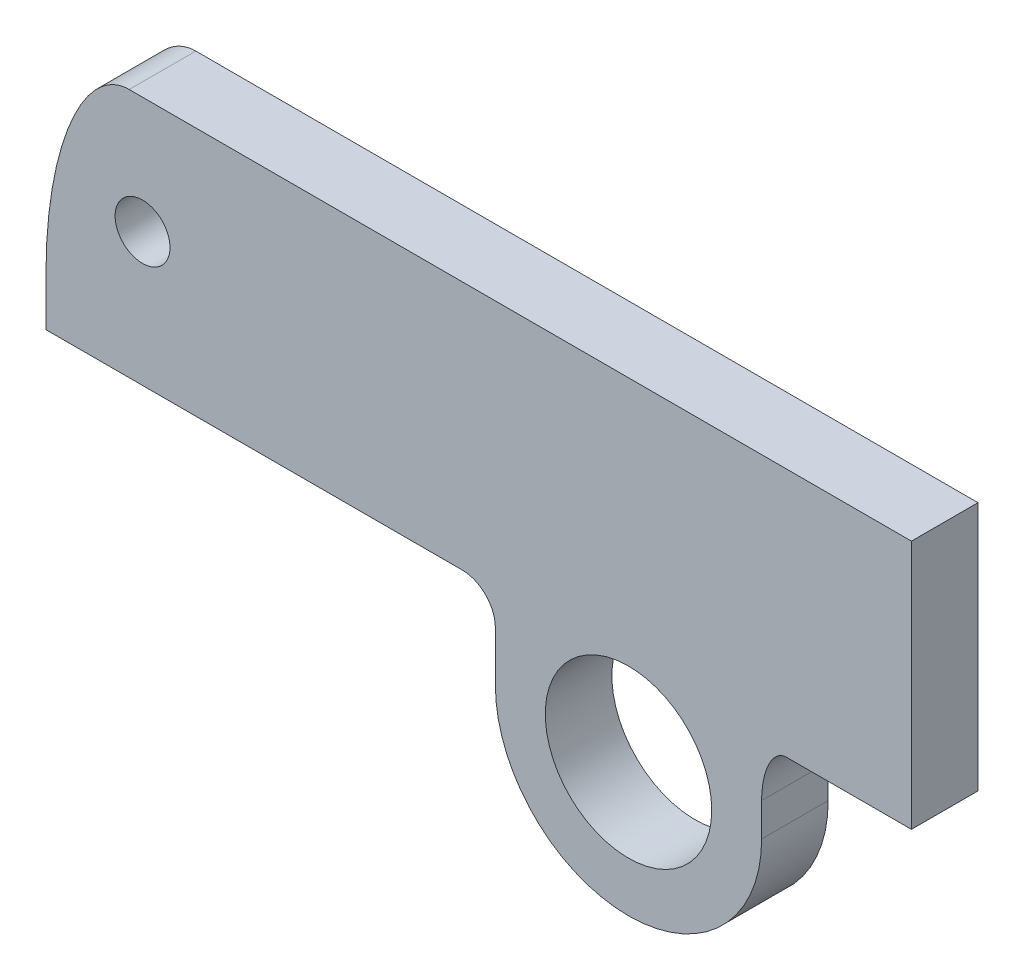
SolidWorks part; units mm, degrees
ref_plane "Plano frontal" through (0, 0, 0) normal (0, 0, 1) x (1, 0, 0)
ref_plane "Plano superior" through (0, 0, 0) normal (0, 1, 0) x (1, 0, 0)
ref_plane "Plano direito" through (0, 0, 0) normal (1, 0, 0) x (0, 0, -1)
sketch "Esboço1" plane through (0, 0, 0) normal (0, 0, 1) x (1, 0, 0)
  line L0 (0, 0) -> (25, 0)
  line L1 (25, 0) -> (25, 28)
  line L3 (-27, 28) -> (-27, 13)
  line L4 (-27, 13) -> (0, 13)
  line L5 (0, 13) -> (0, 0)
  line L10 (-27, 28) -> (25, 28)
  dimension "D1" = 25
  dimension "D2" = 15
  dimension "D3" = 27
  dimension "D4" = 13
extrude "Ressalto-extrusão1" add sketch "Esboço1" along normal blind 4
fillet "Filete3" radius 8 1 edges at (0, 0, 2)
sketch "Esboço2" plane through (0, 0, 4) normal (0, 0, 1) x (1, 0, 0)
  line L0 (-27, 13) -> (0, 13) construction
  line L2 (-27, 28) -> (-27, 13) construction
  circle A1 centre (-21.2, 21) radius 1.65
  circle A2 centre (8, 8) radius 5
  dimension "D1" = 10
  dimension "D2" = 8
  dimension "D4" = 3.3
  dimension "D5" = 5.8
extrude "Corte-extrusão1" cut sketch "Esboço2" against normal through all
fillet "Filete12" radius 5 1 edges at (-27, 28, 2) second distance 12 first distance on face at (-1, 28, 2)
fillet "Filete14" radius 2 1 edges at (0, 13, 2)
sketch "Esboço3" plane through (0, 0, 4) normal (0, 0, 1) x (1, 0, 0)
  line L0 (16, 0) -> (16, 13)
  line L1 (8, 0) -> (25, 0) construction
  line L2 (16, 13) -> (25, 13)
  line L3 (25, 0) -> (25, 28) construction
  line L4 (25, 13) -> (25, 0)
  line L5 (25, 0) -> (16, 0)
  dimension "D1" = 9
  dimension "D2" = 13
extrude "Corte-extrusão2" cut sketch "Esboço3" against normal through all contours L2 L4 L5 L0
fillet "Filete15" radius 8 1 edges at (16, 0, 2)
fillet "Filete16" radius 1.5 1 edges at (16, 13, 2) second distance 3 first distance on face at (20.5, 13, 2)
